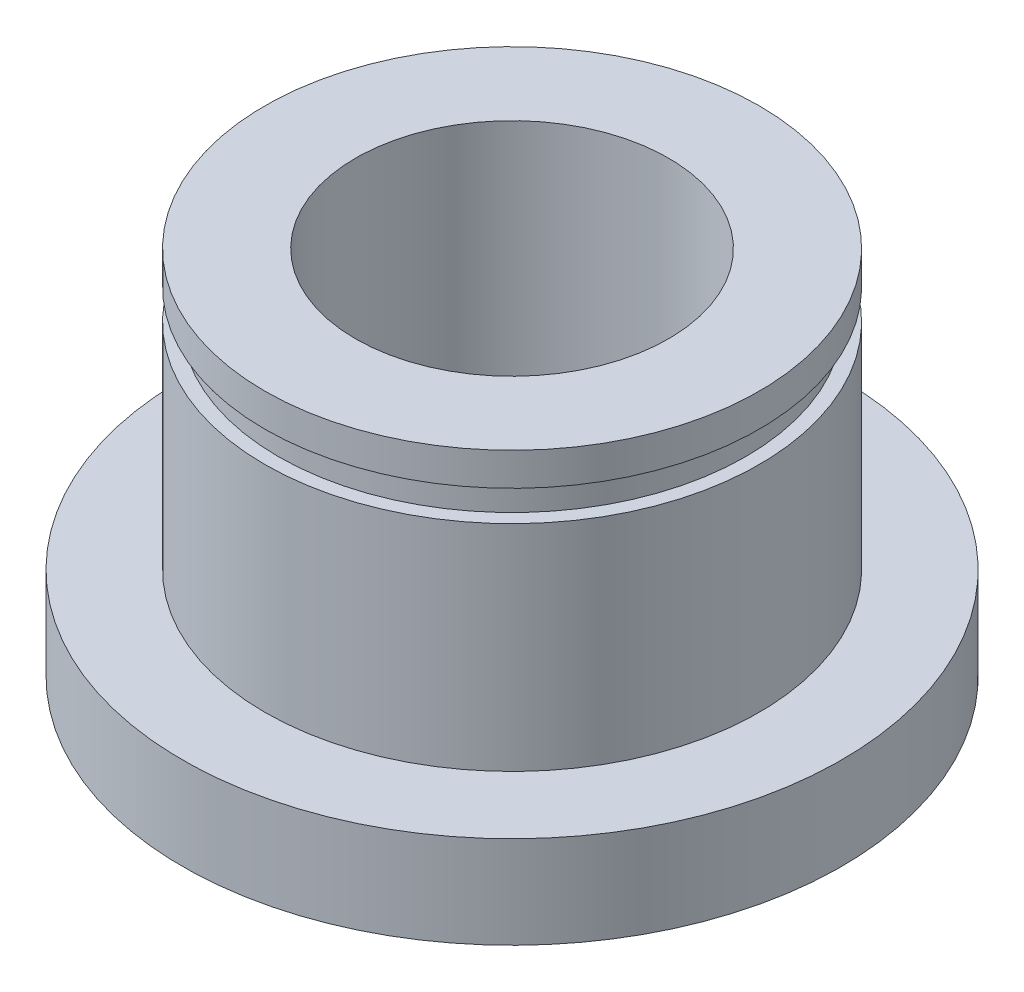
SolidWorks part; units mm, degrees
material "6061-T6 (SS)"
ref_plane "X-Y Datum" through (0, 0, 0) normal (0, 0, 1) x (1, 0, 0)
ref_plane "X-Z Datum" through (0, 0, 0) normal (0, 1, 0) x (1, 0, 0)
ref_plane "Y-Z Datum" through (0, 0, 0) normal (1, 0, 0) x (0, 0, -1)
sketch "Sketch1" plane through (0, 0, 0) normal (1, 0, 0) x (0, 0, -1)
  line L0 (0, 0) -> (0, 8253.6099) construction
  line L1 (0, -4.4609) -> (-7.9375, -4.4609)
  line L2 (-7.9375, -4.4609) -> (-7.9375, -2.2384)
  line L3 (-7.9375, -2.2384) -> (-5.9531, -2.2384)
  line L4 (-5.9531, -2.2384) -> (-5.9531, 2.9305)
  line L7 (-5.6261, 3.6671) -> (-5.9531, 3.6671)
  line L8 (-5.9531, 3.6671) -> (-5.9531, 4.4609)
  line L9 (-5.9531, 4.4609) -> (0, 4.4609)
  line L10 (0, 4.4609) -> (0, -4.4609)
  line L11 (0, 0) -> (-50000, 0) construction
  line L12 (-5.9531, 2.9305) -> (-5.6261, 2.9305)
  line L13 (-5.6261, 2.9305) -> (-5.6261, 3.6671)
  point P9 (0, 0)
  dimension "D1" = 15.875
  dimension "D2" = 11.9062
  dimension "D3" = 2.2225
  dimension "D4" = 11.2522
  dimension "D5" = 0.7937
  dimension "D6" = 5.1689
  dimension "D7" = 0.7366
revolve "Revolve1" add sketch "Sketch1" angle 360 about L0
hole_wizard "19/64 (0.29688) Diameter Hole1" positions "Sketch2" profile "Sketch3" hole size "19/64" standard "ANSI Inch" end condition through all
sketch "Sketch2" plane through (0, 4.4609, 0) normal (0, 1, 0) x (1, 0, 0)
  point P0 (0, 0)
sketch "Sketch3" plane through (0, 4.4609, 0) normal (1, 0, 0) x (0, 0, 1)
  line L0 (0, 0) -> (0, 8.9218)
  line L1 (0, 8.9218) -> (3.7704, 8.9218)
  line L2 (3.7704, 8.9218) -> (3.7704, 0)
  line L5 (3.7704, 0) -> (0, 0)
  line L11 (0, -6.35) -> (0, 107.95) construction
  dimension "Thru Hole Dia." = 7.5408
  dimension "Thru Hole Depth" = 8.9218
chamfer "Chamfer1" distance 0.7937 angle 45 1 edges at (0, -4.4609, 3.7704)
